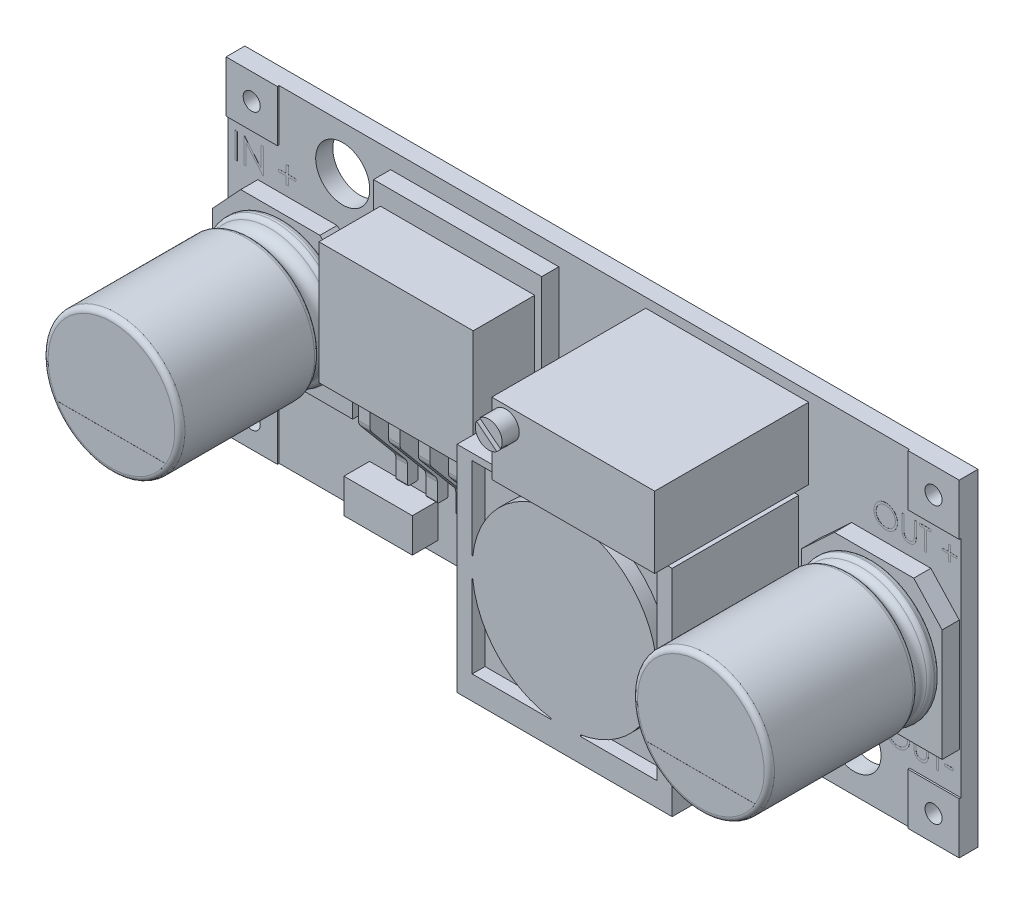
SolidWorks part; units mm, degrees
ref_plane "Front Plane" through (0, 0, 0) normal (0, 0, 1) x (1, 0, 0)
ref_plane "Top Plane" through (0, 0, 0) normal (0, 1, 0) x (1, 0, 0)
ref_plane "Right Plane" through (0, 0, 0) normal (1, 0, 0) x (0, 0, -1)
sketch "Sketch1" plane through (0, 0, 0) normal (0, 0, 1) x (1, 0, 0)
  line L1 (21.4264, -9.5637) -> (-21.4264, -9.5637)
  line L2 (21.4264, -9.5637) -> (21.4264, 9.5637)
  line L3 (21.4264, 9.5637) -> (-21.4264, 9.5637)
  line L4 (-21.4264, -9.5637) -> (-21.4264, 9.5637)
  line L5 (21.4264, -9.5637) -> (-21.4264, 9.5637) construction
  line L6 (21.4264, 9.5637) -> (-21.4264, -9.5637) construction
  circle A0 centre (-14.7064, 6.9537) radius 1.58
  circle A1 centre (15.1764, -6.774) radius 1.58
  point P0 (0, 0)
extrude "Boss-Extrude1" add sketch "Sketch1" along normal blind 1
sketch "Sketch2" plane through (0, 0, 1) normal (0, 0, 1) x (1, 0, 0)
  line L1 (-21.4264, 9.5637) -> (-18.4264, 9.5637)
  line L2 (-21.4264, 9.5637) -> (-21.4264, 6.5637)
  line L3 (-21.4264, 6.5637) -> (-18.4264, 6.5637)
  line L4 (-18.4264, 9.5637) -> (-18.4264, 6.5637)
  line L8 (-18.4264, -9.5637) -> (-18.4264, -6.5637)
  line L9 (-21.4264, -6.5637) -> (-18.4264, -6.5637)
  line L10 (-21.4264, -9.5637) -> (-21.4264, -6.5637)
  line L11 (-21.4264, -9.5637) -> (-18.4264, -9.5637)
  line L12 (21.4264, -9.5637) -> (18.4264, -9.5637)
  line L13 (21.4264, -9.5637) -> (21.4264, -6.5637)
  line L14 (21.4264, -6.5637) -> (18.4264, -6.5637)
  line L15 (18.4264, -9.5637) -> (18.4264, -6.5637)
  line L16 (18.4264, 9.5637) -> (18.4264, 6.5637)
  line L17 (21.4264, 6.5637) -> (18.4264, 6.5637)
  line L18 (21.4264, 9.5637) -> (21.4264, 6.5637)
  line L19 (21.4264, 9.5637) -> (18.4264, 9.5637)
extrude "Boss-Extrude2" add sketch "Sketch2" along normal blind 0.1
sketch "Sketch3" plane through (0, 0, 1.1) normal (0, 0, 1) x (1, 0, 0)
  circle A0 centre (-19.9264, 8.0637) radius 0.5
  circle A1 centre (-19.9264, -8.0637) radius 0.5
  circle A2 centre (19.9264, -8.0637) radius 0.5
  circle A3 centre (19.9264, 8.0637) radius 0.5
extrude "Cut-Extrude1" cut sketch "Sketch3" against normal blind 5
sketch "Sketch4" plane through (0, 0, 1) normal (0, 0, 1) x (1, 0, 0)
  line L5 (-21.3314, 2.3832) -> (-19.6699, 4.175)
  line L6 (-19.6699, 4.175) -> (-15.0378, 4.175)
  line L7 (-21.3314, -4.175) -> (-13.1214, -4.175)
  line L8 (-21.3314, -4.175) -> (-21.3314, 2.3832)
  line L9 (-19.6699, 4.175) -> (-15.0378, 4.175)
  line L10 (-13.1214, -4.175) -> (-13.1214, 2.398)
  line L11 (-21.3314, -4.175) -> (-14.0353, 3.2455) construction
  line L12 (-20.4763, 3.3054) -> (-13.1214, -4.175) construction
  line L13 (-15.0378, 4.175) -> (-13.1214, 2.398)
  line L14 (20.4763, 3.3054) -> (13.1214, -4.175) construction
  line L15 (21.3314, -4.175) -> (14.0353, 3.2455) construction
  line L16 (15.0378, 4.175) -> (13.1214, 2.398)
  line L17 (13.1214, -4.175) -> (13.1214, 2.398)
  line L18 (19.6699, 4.175) -> (15.0378, 4.175)
  line L19 (21.3314, -4.175) -> (21.3314, 2.3832)
  line L20 (21.3314, -4.175) -> (13.1214, -4.175)
  line L21 (19.6699, 4.175) -> (15.0378, 4.175)
  line L22 (21.3314, 2.3832) -> (19.6699, 4.175)
  point P13 (-17.2264, 0)
  point P28 (17.2264, 0)
extrude "Boss-Extrude3" add sketch "Sketch4" along normal blind 1 contours L13 L6 L5 L8 L7 L10 | L19 L22 L18 L16 L17 L20 region at (-17.2358, -0.1748, 1) region at (17.2358, -0.1748, 1)
sketch "Sketch5" plane through (0, 0, 2) normal (0, 0, 1) x (1, 0, 0)
  circle A0 centre (-17.2264, 0) radius 4.105
  circle A1 centre (17.2264, 0) radius 4.105
sketch "Sketch6" plane through (0, 0, 1) normal (0, 0, 1) x (1, 0, 0)
  line L5 (-11.9064, 8.5637) -> (-2.0764, 8.5637)
  line L6 (-11.9064, 8.5637) -> (-11.9064, -0.1863)
  line L7 (-11.9064, -0.1863) -> (-2.0764, -0.1863)
  line L8 (-2.0764, 8.5637) -> (-2.0764, -0.1863)
extrude "Boss-Extrude5" add sketch "Sketch6" along normal blind 4.6
sketch "Sketch7" plane through (0, 0, 5.6) normal (0, 0, 1) x (1, 0, 0)
  line L3 (-11.4988, 7.4182) -> (-2.4839, 7.4182)
  line L4 (-11.4988, 0.2879) -> (-2.4839, 0.2879)
  line L5 (-11.4988, 0.2879) -> (-11.4988, 7.4182)
  line L7 (-2.4839, 0.2879) -> (-2.4839, 7.4182)
  line L11 (-11.9064, -0.1863) -> (-2.0764, -0.1863)
  line L12 (-11.9064, -0.1863) -> (-11.9064, 8.5637)
  line L13 (-11.9064, 8.5637) -> (-2.0764, 8.5637)
  line L14 (-2.0764, -0.1863) -> (-2.0764, 8.5637)
  point P6 (-6.9914, 4.1887)
  point P13 (-6.9914, 4.1887)
extrude "Cut-Extrude2" cut sketch "Sketch7" against normal blind 3.6
sketch "Sketch8" plane through (0, 0.2879, 0) normal (0, -1, 0) x (-1, 0, 0)
  line L0 (9.1927, -4.7708) -> (9.1927, -1.0208)
  line L1 (10.9427, -4.7708) -> (10.2713, -4.7708)
  line L2 (10.9427, -4.7708) -> (10.9427, -1.0208)
  line L3 (10.9427, -1.0208) -> (10.2713, -1.0208)
  line L4 (10.2713, -4.7708) -> (10.2713, -1.0208)
  line L5 (9.1927, -4.7708) -> (8.5213, -4.7708)
  line L6 (8.5213, -4.7708) -> (8.5213, -1.0208)
  line L7 (9.1927, -1.0208) -> (8.5213, -1.0208)
  line L8 (7.4427, -4.7708) -> (7.4427, -1.0208)
  line L9 (7.4427, -4.7708) -> (6.7713, -4.7708)
  line L10 (6.7713, -4.7708) -> (6.7713, -1.0208)
  line L11 (7.4427, -1.0208) -> (6.7713, -1.0208)
  line L12 (5.6927, -4.7708) -> (5.6927, -1.0208)
  line L13 (5.6927, -4.7708) -> (5.0213, -4.7708)
  line L14 (5.0213, -4.7708) -> (5.0213, -1.0208)
  line L15 (5.6927, -1.0208) -> (5.0213, -1.0208)
  line L16 (3.9427, -4.7708) -> (3.9427, -1.0208)
  line L17 (3.9427, -4.7708) -> (3.2713, -4.7708)
  line L18 (3.2713, -4.7708) -> (3.2713, -1.0208)
  line L19 (3.9427, -1.0208) -> (3.2713, -1.0208)
  dimension "D1" = 5
extrude "Boss-Extrude6" add sketch "Sketch8" along normal blind 8
sketch "Sketch10" plane through (0, 0, 1) normal (0, 0, 1) x (1, 0, 0)
  line L5 (11.9464, -8.5637) -> (-0.6236, -8.5637)
  line L6 (11.9464, -8.5637) -> (11.9464, 4.0063)
  line L7 (11.9464, 4.0063) -> (-0.6236, 4.0063)
  line L8 (-0.6236, -8.5637) -> (-0.6236, 4.0063)
extrude "Boss-Extrude7" add sketch "Sketch10" along normal blind 7.4
sketch "Sketch11" plane through (0, 0, 8.4) normal (0, 0, 1) x (1, 0, 0)
  line L0 (0.2614, -1.1682) -> (0.2922, -1.2029)
  line L3 (0.2614, -2.3394) -> (0.2922, -2.3545)
  line L4 (0.2614, -7.1787) -> (4.8799, -7.1787)
  line L5 (0.2614, -7.1787) -> (0.2614, -2.3394)
  line L6 (0.2614, 3.6213) -> (4.9528, 3.6213)
  line L7 (11.0614, -7.1787) -> (11.0614, -2.7691)
  line L8 (0.2614, -7.1787) -> (11.0614, 3.6213) construction
  line L9 (0.2614, 3.6213) -> (11.0614, -7.1787) construction
  line L10 (4.9528, 3.6213) -> (4.9528, 3.5746)
  line L11 (6.2806, 3.6213) -> (6.2806, 3.5857)
  line L12 (10.9698, -0.7882) -> (11.0614, -0.7882)
  line L13 (10.9698, -2.7691) -> (11.0614, -2.7691)
  line L14 (4.8799, -7.1787) -> (4.8799, -7.1218)
  line L15 (6.582, -7.1787) -> (6.582, -7.0996)
  line L16 (6.582, -7.1787) -> (11.0614, -7.1787)
  line L17 (0.2614, -1.1682) -> (0.2614, 3.6213)
  line L18 (6.2806, 3.6213) -> (11.0614, 3.6213)
  line L19 (11.0614, -0.7882) -> (11.0614, 3.6213)
  arc A0 (6.582, -7.0996) -> (10.9698, -2.7691) centre (5.6614, -1.7787) ccw
  arc A1 (0.2922, -2.3545) -> (4.8799, -7.1218) centre (5.6614, -1.7787) ccw
  arc A2 (4.9528, 3.5746) -> (0.2922, -1.2029) centre (5.6614, -1.7787) ccw
  arc A3 (10.9698, -0.7882) -> (6.2806, 3.5857) centre (5.6614, -1.7787) ccw
  point P6 (5.6614, -1.7787)
extrude "Cut-Extrude7" cut sketch "Sketch11" against normal blind 0.75
sketch "Sketch13" plane through (0, 0, 1) normal (0, 0, 1) x (1, 0, 0)
  line L1 (12.527, 4.8371) -> (3.007, 4.8371)
  line L2 (12.527, 4.8371) -> (12.527, 9.0071)
  line L3 (12.527, 9.0071) -> (3.007, 9.0071)
  line L4 (3.007, 4.8371) -> (3.007, 9.0071)
extrude "Boss-Extrude8" add sketch "Sketch13" along normal blind 9
sketch "Sketch14" plane through (0, 0, 10) normal (0, 0, 1) x (1, 0, 0)
  circle A0 centre (3.8265, 8.0224) radius 0.7858
extrude "Boss-Extrude9" add sketch "Sketch14" along normal blind 1
sketch "Sketch16" plane through (0, 0, 11) normal (0, 0, 1) x (1, 0, 0)
  line L0 (3.1748, 8.7082) -> (4.6558, 7.5307)
  line L1 (4.6558, 7.5307) -> (4.4523, 7.2747)
  line L2 (4.4523, 7.2747) -> (2.9713, 8.4522)
  line L3 (2.9713, 8.4522) -> (3.1748, 8.7082)
extrude "Cut-Extrude8" cut sketch "Sketch16" against normal blind 0.4
sketch "Sketch17" plane through (0, 0, 0) normal (0, 1, 0) x (1, 0, 0)
  line L0 (-17.2264, -2) -> (-17.2264, -12)
  line L1 (-21.3314, -2) -> (-13.1214, -2) construction
  line L2 (-17.2264, -12) -> (-20.9264, -12)
  line L3 (-21.2264, -11.7) -> (-21.2264, -4.1269)
  line L4 (-20.9264, -2) -> (-17.2264, -2)
  line L5 (-21.2264, -2.4494) -> (-21.2264, -2.3)
  arc A0 (-21.0274, -2.7319) -> (-21.0274, -3.8444) centre (-21.2264, -3.2881) cw
  arc A1 (-20.9264, -2) -> (-21.2264, -2.3) centre (-20.9264, -2.3) ccw
  arc A2 (-21.2264, -2.4494) -> (-21.0274, -2.7319) centre (-20.9264, -2.4494) ccw
  arc A3 (-21.0274, -3.8444) -> (-21.2264, -4.1269) centre (-20.9264, -4.1269) ccw
  arc A4 (-21.2264, -11.7) -> (-20.9264, -12) centre (-20.9264, -11.7) ccw
  point P12 (-21.2264, -2)
  point P15 (-21.2264, -2.6973)
  point P20 (-21.2264, -12)
  dimension "D3" = 0.3
  dimension "D4" = 0.3
  dimension "D5" = 0.3
  dimension "D6" = 0.3
  dimension "D1" = 10
  dimension "D2" = 4
revolve "Revolve1" add sketch "Sketch17" angle 360 about L0
sketch "Sketch18" plane through (0, 0, 0) normal (0, 1, 0) x (1, 0, 0)
  line L0 (17.2264, -2) -> (17.2264, -12)
  line L1 (21.3314, -2) -> (13.1214, -2) construction
  line L2 (17.2264, -12) -> (20.9264, -12)
  line L3 (21.2264, -11.7) -> (21.2264, -3.6026)
  line L4 (20.9264, -2) -> (17.2264, -2)
  line L5 (21.2264, -2.364) -> (21.2264, -2.3)
  arc A0 (21.0572, -2.634) -> (21.0572, -3.3326) centre (21.2264, -2.9833) ccw
  arc A1 (21.2264, -11.7) -> (20.9264, -12) centre (20.9264, -11.7) cw
  arc A2 (21.0572, -3.3326) -> (21.2264, -3.6026) centre (20.9264, -3.6026) cw
  arc A3 (21.0572, -2.634) -> (21.2264, -2.364) centre (20.9264, -2.364) ccw
  arc A4 (20.9264, -2) -> (21.2264, -2.3) centre (20.9264, -2.3) cw
  point P11 (21.2264, -12)
  point P16 (21.2264, -2.5952)
  point P19 (21.2264, -2)
  dimension "D3" = 0.3
  dimension "D1" = 10
  dimension "D2" = 4
revolve "Revolve2" add sketch "Sketch18" angle 360 about L0
sketch "Sketch20" plane through (-10.9427, 0, 0) normal (-1, 0, 0) x (0, 0, 1)
  line L0 (3.8444, 0.2896) -> (3.8444, -2.2336)
  line L1 (3.8444, 3.801) -> (3.8444, -3.801) construction
  line L2 (3.7275, -2.5549) -> (1.7713, -4.8877)
  line L3 (1.6544, -5.209) -> (1.6544, -6.2296)
  line L4 (1.5544, -6.3296) -> (1.1197, -6.3296)
  line L5 (1.0208, -7.7121) -> (1.0208, -0.1863) construction
  line L6 (1.0197, -6.2308) -> (1.0208, -4.4558)
  line L8 (1.1189, -4.3365) -> (2.9146, -2.1951)
  line L9 (8.1377, -10.4913) -> (1.0208, -10.4913)
  line L10 (3.0315, 0.2896) -> (3.0315, -1.8738)
  line L11 (1.0208, -4.4558) -> (1.1189, -4.3365)
  line L12 (3.0315, 0.2896) -> (1, 0.2896)
  line L13 (8.1377, -10.4913) -> (8.1377, 0.2896)
  line L14 (8.1377, 0.2896) -> (3.8444, 0.2896)
  line L15 (1, 6.5637) -> (1, -6.5637) construction
  line L16 (1, 0.2896) -> (1.0208, -10.4913)
  arc A1 (1.6544, -5.209) -> (1.7713, -4.8877) centre (2.1544, -5.209) cw
  arc A2 (2.9146, -2.1951) -> (3.0315, -1.8738) centre (2.5315, -1.8738) ccw
  arc A3 (3.8444, -2.2336) -> (3.7275, -2.5549) centre (3.3444, -2.2336) cw
  arc A4 (1.1197, -6.3296) -> (1.0197, -6.2308) centre (1.1197, -6.2296) cw
  arc A5 (1.5544, -6.3296) -> (1.6544, -6.2296) centre (1.5544, -6.2296) ccw
  point P23 (3.8444, -2.4155)
  point P26 (1.0208, -6.3296)
  dimension "D2" = 0.1
extrude "Cut-Extrude10" cut sketch "Sketch20" against normal blind 9
sketch "Sketch21" plane through (-10.9427, 0, 0) normal (1, 0, 0) x (0, 0, -1)
  line L0 (-2, -0.1841) -> (-1, -0.1841)
  line L1 (-2, -4.175) -> (-2, 2.3832) construction
  line L2 (-1, -4.175) -> (-1, 2.3832) construction
  line L3 (-2, -0.1841) -> (-2, 0.2879)
  line L4 (-1, -0.1841) -> (-1, 0.2879)
  line L5 (-1, 0.2879) -> (-2, 0.2879)
extrude "Boss-Extrude11" add sketch "Sketch21" along normal blind 8.8665
sketch "Sketch24" plane through (0, 0, 0) normal (0, 0, -1) x (-1, 0, 0)
  text T0 "<b>DC to DC</b>"
extrude "Boss-Extrude15" add sketch "Sketch24" along normal blind 0.005
sketch "Sketch25" plane through (0, 0, 12) normal (0, 0, 1) x (1, 0, 0)
  line L0 (-20.4073, -1.8899) -> (-14.0455, -1.8899)
  line L1 (14.0455, -1.8899) -> (20.4073, -1.8899)
  circle A0 centre (-17.2264, 0) radius 3.7 construction
  arc A1 (-20.4073, -1.8899) -> (-14.0455, -1.8899) centre (-17.2264, 0) ccw
  circle A2 centre (17.2264, 0) radius 3.7 construction
  arc A3 (14.0455, -1.8899) -> (20.4073, -1.8899) centre (17.2264, 0) ccw
extrude "Boss-Extrude16" add sketch "Sketch25" along normal blind 0.005
sketch "Sketch26" plane through (0, 0, 1) normal (0, 0, 1) x (1, 0, 0)
  line L0 (-9.1386, -6.8179) -> (-13.1386, -6.8179)
  line L1 (-9.1386, -6.8179) -> (-9.1386, -8.8179)
  line L2 (-9.1386, -8.8179) -> (-13.1386, -8.8179)
  line L3 (-13.1386, -8.8179) -> (-13.1386, -6.8179)
  dimension "D1" = 2
  dimension "D2" = 4
extrude "Boss-Extrude18" add sketch "Sketch26" along normal blind 1.5
sketch "Sketch28" plane through (0, 0, 1) normal (0, 0, 1) x (1, 0, 0)
  text T0 "IN-" font "Century Gothic" height 1.5
extrude "Boss-Extrude19" add sketch "Sketch28" along normal blind 0.005
sketch "Sketch29" plane through (0, 0, 1) normal (0, 0, 1) x (1, 0, 0)
  text T0 "IN +" font "Century Gothic" height 1.5
extrude "Boss-Extrude20" add sketch "Sketch29" along normal blind 0.005
sketch "Sketch30" plane through (0, 0, 1) normal (0, 0, 1) x (1, 0, 0)
  text T0 "OUT +" font "Century Gothic" height 1.3
extrude "Boss-Extrude21" add sketch "Sketch30" along normal blind 0.005
sketch "Sketch32" plane through (0, 0, 1) normal (0, 0, 1) x (1, 0, 0)
  text T0 "OUT-" font "Century Gothic" height 1.3
extrude "Boss-Extrude23" add sketch "Sketch32" along normal blind 0.005
